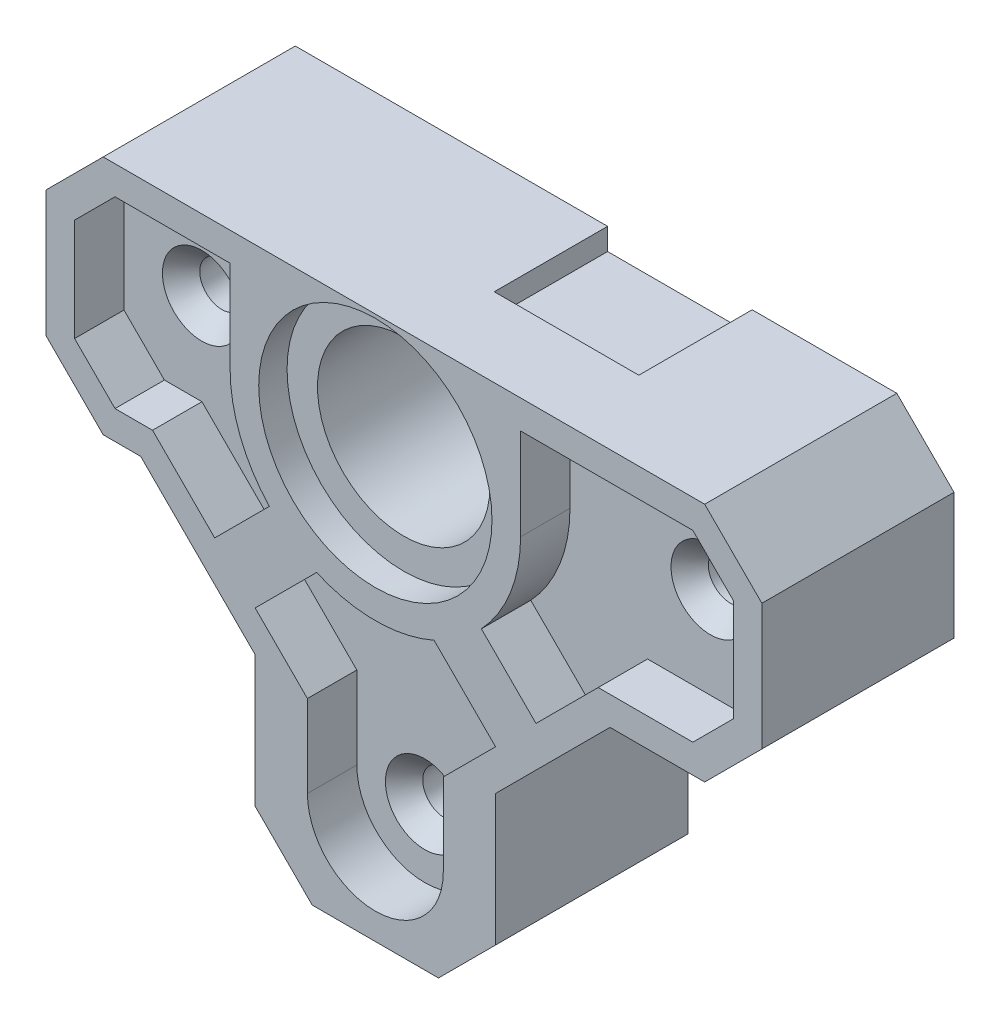
SolidWorks part; units mm, degrees
material "PET"
ref_plane "Front" through (0, 0, 0) normal (0, 0, 1) x (1, 0, 0)
ref_plane "Top" through (0, 0, 0) normal (0, 1, 0) x (1, 0, 0)
ref_plane "Right" through (0, 0, 0) normal (1, 0, 0) x (0, 0, -1)
sketch "Sketch1" plane through (0, 0, 0) normal (0, 0, 1) x (1, 0, 0)
  line L0 (-6.6802, -13.0302) -> (-6.6802, -23.495) construction
  line L1 (21.463, 6.6802) -> (-18.288, 6.6802)
  line L2 (21.463, 6.6802) -> (21.463, -6.6802)
  line L3 (21.463, -6.6802) -> (6.6802, -6.6802)
  line L4 (-18.288, 6.6802) -> (-18.288, -6.6802)
  line L5 (6.6802, -23.495) -> (-6.6802, -23.495)
  line L6 (6.6802, -23.495) -> (6.6802, -6.6802)
  line L8 (-6.6802, -23.495) -> (-6.6802, -6.6802)
  line L9 (-6.6802, -6.6802) -> (-18.288, -6.6802)
extrude "Boss-Extrude1" add sketch "Sketch1" along normal up to surface (10.668 mm away)
hole_wizard "CSK for #2 Flat Head Machine Screw1" positions "Sketch2" profile "Sketch3" countersink size "#2" standard "ANSI Inch" end condition through all
sketch "Sketch2" plane through (0, 0, 10.668) normal (0, 0, 1) x (1, 0, 0)
  line L0 (6.6802, -13.0302) -> (-6.6802, -13.0302) construction
  line L1 (6.6802, -6.6802) -> (6.6802, -23.495) construction
  line L2 (-6.6802, -23.495) -> (-6.6802, -6.6802) construction
  line L4 (0, -13.0302) -> (0, -23.495) construction
  line L5 (6.6802, -23.495) -> (-6.6802, -23.495) construction
  point P0 (15.8591, 0)
  point P3 (-12.3825, 0)
  point P7 (0, -18.2626)
sketch "Sketch3" plane through (15.8591, 0, 10.668) normal (1, 0, 0) x (0, -1, 0)
  line L0 (0, 0) -> (0, 10.668)
  line L1 (0, 10.668) -> (1.2192, 10.668)
  line L2 (1.2192, 10.668) -> (1.2192, 3.8535)
  line L3 (1.2192, 3.8535) -> (2.1844, 2.7432)
  line L4 (2.1844, 2.7432) -> (2.1844, 0)
  line L6 (2.1844, 0) -> (0, 0)
  line L7 (-1.2192, 3.8535) -> (-2.1844, 2.7432) construction
  line L11 (0, -6.35) -> (0, 107.95) construction
  dimension "Thru Hole Dia." = 2.4384
  dimension "Thru Hole Depth" = 10.668
  dimension "C'Sink Dia." = 4.3688
  dimension "C'Sink Angle" = 82
  dimension "Head Clearance" = 2.7432
sketch "Sketch4" plane through (0, 0, 10.668) normal (0, 0, 1) x (1, 0, 0)
  circle A0 centre (0, 0) radius 6.477
  dimension "D1" = 12.954
extrude "Cut-Extrude1" cut sketch "Sketch4" against normal blind 1.5748
sketch "Sketch5" plane through (0, 0, 10.668) normal (0, 0, 1) x (1, 0, 0)
  circle A0 centre (0, 0) radius 4.7879
  dimension "D1" = 9.5758
extrude "Cut-Extrude2" cut sketch "Sketch5" against normal through all
sketch "Sketch6" plane through (0, 0, 0) normal (0, 0, -1) x (-1, 0, 0)
  line L8 (-10.2553, 5.4667) -> (-2.2289, 5.4667)
  line L9 (-10.2553, 15.4997) -> (-10.2553, 5.4667)
  line L10 (-2.2289, 15.4997) -> (-10.2553, 15.4997)
  line L11 (-2.2289, 5.4667) -> (-2.2289, 15.4997)
  line L12 (-10.2553, 5.4667) -> (-2.2289, 5.4667)
  line L13 (-10.2553, 15.4997) -> (-10.2553, 5.4667)
  line L14 (-2.2289, 15.4997) -> (-10.2553, 15.4997)
  line L15 (-2.2289, 5.4667) -> (-2.2289, 15.4997)
  dimension "D1" = 0.762
extrude "Cut-Extrude3" cut sketch "Sketch6" against normal blind 5.08
draft "Draft2" type of draft neutral plane draft angle 45 faces to draft 1 face at (6.2421, 6.0735, 5.08) neutral plane through (10.2553, 5.4667, 5.08) neutral plane normal (0, 1, 0) parameters "D1"=45
chamfer "Chamfer1" distance 3.175 angle 45 6 edges at (-18.288, 6.6802, 5.334) (21.463, 6.6802, 5.334) (21.463, -6.6802, 5.334) (6.6802, -23.495, 5.334) (-6.6802, -23.495, 5.334) (-18.288, -6.6802, 5.334)
chamfer "Chamfer2" distance 6.35 angle 45 2 edges at (-6.6802, -6.6802, 5.334) (6.6802, -6.6802, 5.334)
sketch "Sketch7" plane through (0, 0, 10.668) normal (0, 0, 1) x (1, 0, 0)
  line L3 (3.7719, -13.6934) -> (6.6751, -10.7902)
  line L4 (12.3726, -5.0927) -> (17.6304, -5.0927)
  line L5 (17.6304, -5.0927) -> (19.8755, -2.8476)
  line L6 (19.8755, -2.8476) -> (19.8755, 2.8476)
  line L7 (19.8755, 2.8476) -> (17.6304, 5.0927)
  line L8 (17.6304, 5.0927) -> (8.0645, 5.0927)
  line L9 (-14.4554, 5.0927) -> (-16.7005, 2.8476)
  line L10 (-16.7005, 2.8476) -> (-16.7005, -2.8476)
  line L11 (-16.7005, -2.8476) -> (-14.4554, -5.0927)
  line L12 (-14.4554, -5.0927) -> (-12.3726, -5.0927)
  line L13 (-12.3726, -5.0927) -> (-8.9202, -8.5451)
  line L16 (-3.5052, -23.495) -> (3.5052, -23.495)
  line L17 (3.5052, -23.495) -> (6.6802, -20.32)
  line L18 (6.6802, -20.32) -> (6.6802, -13.0302)
  line L19 (6.6802, -13.0302) -> (13.0302, -6.6802)
  line L20 (13.0302, -6.6802) -> (18.288, -6.6802)
  line L21 (18.288, -6.6802) -> (21.463, -3.5052)
  line L22 (21.463, -3.5052) -> (21.463, 3.5052)
  line L23 (21.463, 3.5052) -> (18.288, 6.6802)
  line L24 (18.288, 6.6802) -> (-15.113, 6.6802)
  line L25 (-15.113, 6.6802) -> (-18.288, 3.5052)
  line L26 (-18.288, 3.5052) -> (-18.288, -3.5052)
  line L27 (-18.288, -3.5052) -> (-15.113, -6.6802)
  line L28 (-15.113, -6.6802) -> (-13.0302, -6.6802)
  line L29 (-13.0302, -6.6802) -> (-6.6802, -13.0302)
  line L30 (-6.6802, -13.0302) -> (-6.6802, -20.32)
  line L31 (-6.6802, -20.32) -> (-3.5052, -23.495)
  line L32 (-3.5052, -23.495) -> (3.5052, -23.495) construction
  line L33 (3.5052, -23.495) -> (6.6802, -20.32) construction
  line L34 (6.6802, -20.32) -> (6.6802, -13.0302) construction
  line L35 (6.6802, -13.0302) -> (13.0302, -6.6802) construction
  line L36 (13.0302, -6.6802) -> (18.288, -6.6802) construction
  line L37 (18.288, -6.6802) -> (21.463, -3.5052) construction
  line L38 (21.463, -3.5052) -> (21.463, 3.5052) construction
  line L39 (21.463, 3.5052) -> (18.288, 6.6802) construction
  line L40 (18.288, 6.6802) -> (-15.113, 6.6802) construction
  line L41 (-15.113, 6.6802) -> (-18.288, 3.5052) construction
  line L42 (-18.288, 3.5052) -> (-18.288, -3.5052) construction
  line L43 (-18.288, -3.5052) -> (-15.113, -6.6802) construction
  line L44 (-15.113, -6.6802) -> (-13.0302, -6.6802) construction
  line L45 (-13.0302, -6.6802) -> (-6.6802, -13.0302) construction
  line L46 (-6.6802, -13.0302) -> (-6.6802, -20.32) construction
  line L47 (-6.6802, -20.32) -> (-3.5052, -23.495) construction
  line L48 (-8.0645, 5.0927) -> (-14.4554, 5.0927)
  line L49 (17.6304, 5.0927) -> (-14.4554, 5.0927) construction
  line L50 (5.0927, -19.6624) -> (5.0927, -12.3726) construction
  line L51 (-5.0927, -12.3726) -> (-5.0927, -19.6624) construction
  line L52 (-5.0927, -19.6624) -> (-2.8476, -21.9075) construction
  line L53 (-2.8476, -21.9075) -> (2.8476, -21.9075) construction
  line L54 (2.8476, -21.9075) -> (5.0927, -19.6624) construction
  line L55 (3.7719, -18.2626) -> (3.7719, -13.6934)
  line L56 (5.0927, -12.3726) -> (12.3726, -5.0927) construction
  line L57 (-3.7719, -18.2626) -> (-3.7719, -13.6934)
  line L58 (-12.3726, -5.0927) -> (-5.0927, -12.3726) construction
  line L59 (8.0645, 0) -> (8.0645, 5.0927)
  line L60 (-8.0645, 0) -> (-8.0645, 5.0927)
  line L61 (8.9202, -10.7902) -> (4.6903, -6.5603) construction
  line L62 (8.9202, -8.5451) -> (5.8869, -5.5118)
  line L63 (6.6751, -10.7902) -> (3.2608, -7.3759)
  line L64 (9.4282, -9.0531) -> (5.8128, -5.4378) construction
  line L65 (7.1831, -11.2982) -> (3.5678, -7.6828) construction
  line L66 (0, 0) -> (0, -23.495) construction
  line L67 (-8.9202, -8.5451) -> (-5.8869, -5.5118)
  line L68 (-6.6751, -10.7902) -> (-3.2608, -7.3759)
  line L69 (8.9202, -8.5451) -> (12.3726, -5.0927)
  line L70 (8.3057, -10.1757) -> (4.6903, -6.5603) construction
  line L71 (-6.6751, -10.7902) -> (-3.7719, -13.6934)
  arc A0 (5.8869, -5.5118) -> (8.0645, 0) centre (0, 0) ccw
  arc A1 (-3.2608, -7.3759) -> (3.2608, -7.3759) centre (0, 0) ccw
  circle A2 centre (0, 0) radius 8.0645
  arc A3 (-8.0645, 0) -> (-5.8869, -5.5118) centre (0, 0) ccw
  circle A8 centre (0, -18.2626) radius 3.7719
  arc A9 (-3.7719, -18.2626) -> (3.7719, -18.2626) centre (0, -18.2626) ccw
  dimension "D5" = 1.5875
  dimension "D1" = 0
  dimension "D2" = 1.5875
  dimension "D3" = 1.5875
  dimension "D4" = 1.5875
  dimension "D6" = 1.5875
extrude "Cut-Extrude4" cut sketch "Sketch7" against normal blind 2.7432
